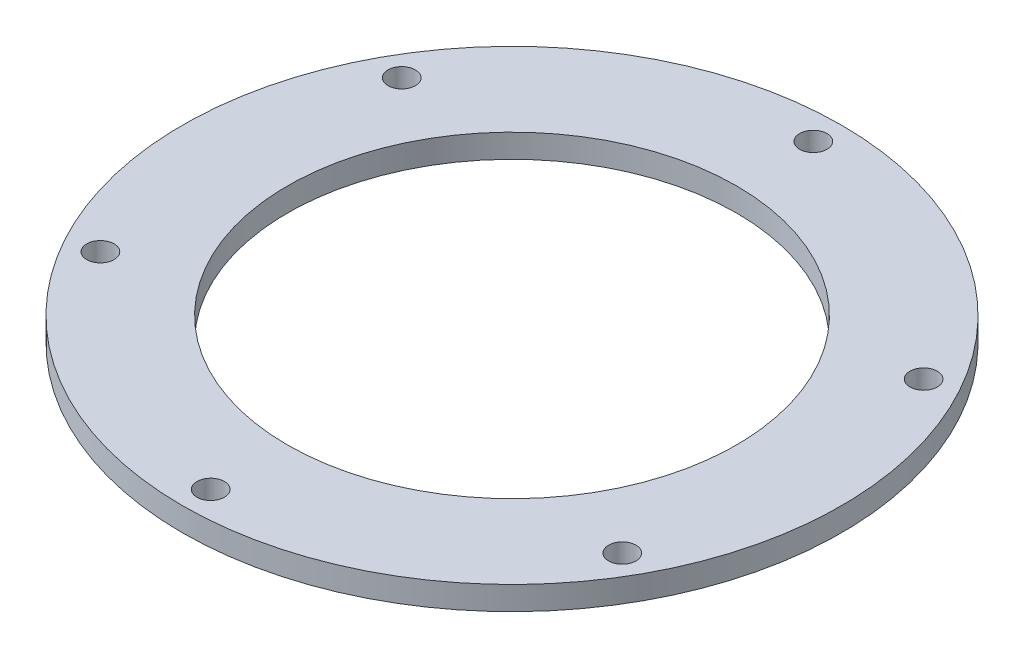
SolidWorks part; units mm, degrees
ref_plane "Front Plane" through (0, 0, 0) normal (0, 0, 1) x (1, 0, 0)
ref_plane "Top Plane" through (0, 0, 0) normal (0, 1, 0) x (1, 0, 0)
ref_plane "Right Plane" through (0, 0, 0) normal (1, 0, 0) x (0, 0, -1)
sketch "Sketch1" plane through (0, 0, 0) normal (0, 1, 0) x (1, 0, 0)
  circle A0 centre (0, 0) radius 40.64 construction
  circle A1 centre (0, 0) radius 44.45
  circle A2 centre (0, 0) radius 30.2759
  dimension "D1" = 81.28
  dimension "D2" = 88.9
  dimension "D3" = 60.5518
extrude "Boss-Extrude1" add sketch "Sketch1" along normal blind 3.175
hole_wizard "#6 Clearance Hole1" positions "Sketch2" profile "Sketch3" hole size "#6" standard "ANSI Inch" end condition up to next
sketch "Sketch2" plane through (0, 3.175, 0) normal (0, 1, 0) x (1, 0, 0)
  line L0 (0, 0) -> (0, 40.64) construction
  circle A0 centre (0, 0) radius 40.64
  point P0 (0, 40.64)
  dimension "D1" = 81.28
sketch "Sketch3" plane through (0, 3.175, -40.64) normal (1, 0, 0) x (0, 0, 1)
  line L0 (0, 0) -> (0, 3.176)
  line L1 (0, 3.176) -> (1.8478, 3.176)
  line L2 (1.8478, 3.176) -> (1.8478, 0)
  line L5 (1.8478, 0) -> (0, 0)
  line L11 (0, -6.35) -> (0, 107.95) construction
  dimension "Thru Hole Dia." = 3.6957
  dimension "Thru Hole Depth" = 3.176
pattern_circular "CirPattern1" count 6 over 360 about axis through (0, 3.175, 0) along (0, 1, 0) of "#6 Clearance Hole1"
